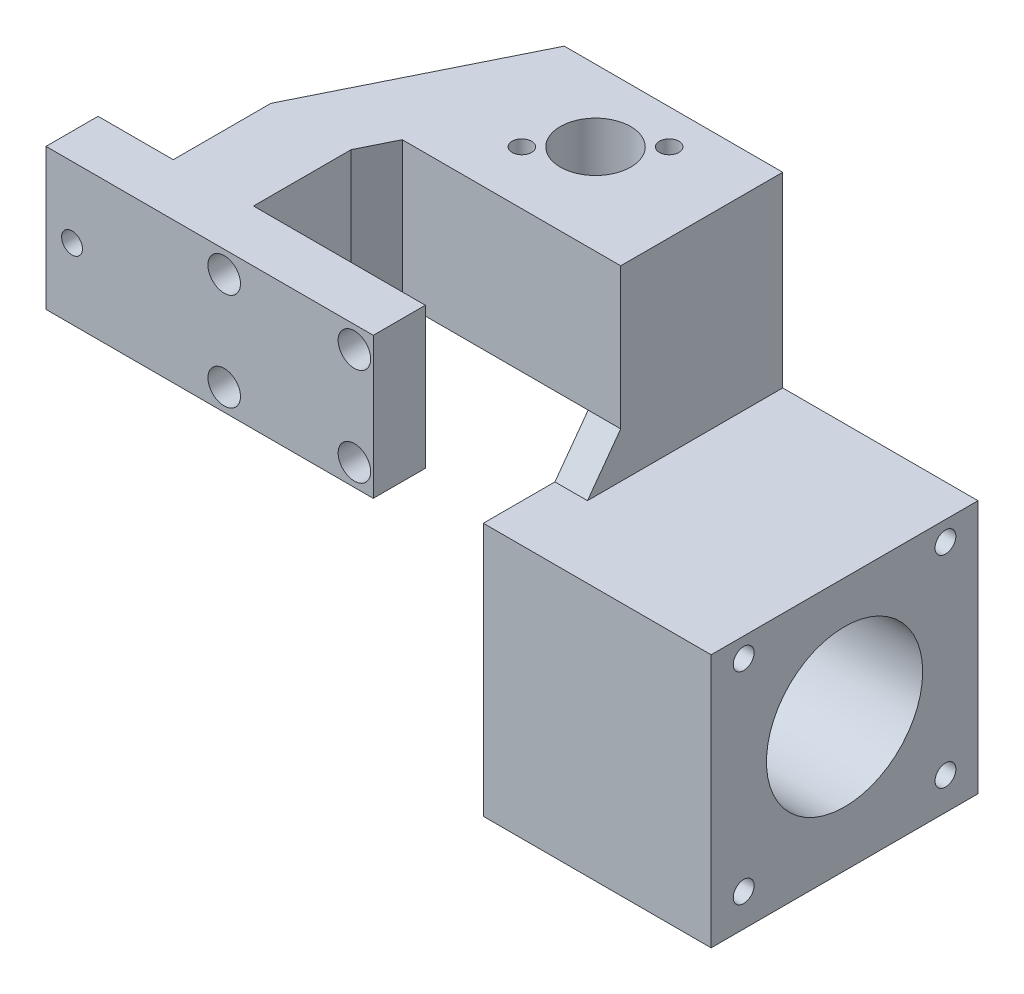
SolidWorks part; units mm, degrees
ref_plane "Přední rovina" through (0, 0, 0) normal (0, 0, 1) x (1, 0, 0)
ref_plane "Horní rovina" through (0, 0, 0) normal (0, 1, 0) x (1, 0, 0)
ref_plane "Pravá rovina" through (0, 0, 0) normal (1, 0, 0) x (0, 0, -1)
sketch "Skica1" plane through (0, 0, 0) normal (0, 0, 1) x (1, 0, 0)
  line L1 (16.212, -19.9414) -> (-34.0669, -19.9414)
  line L2 (16.212, -19.9414) -> (16.212, 1.7586)
  line L3 (16.212, 1.7586) -> (-34.0669, 1.7586)
  line L4 (-34.0669, -19.9414) -> (-34.0669, 1.7586)
  circle A0 centre (13.312, -16.5914) radius 1.6
  circle A1 centre (-6.688, -16.5914) radius 1.6
  circle A2 centre (-6.688, -1.5914) radius 1.6
  circle A3 centre (13.312, -1.5914) radius 1.6
  dimension "D1" = 3.2
  dimension "D2" = 2
  dimension "D3" = 2
extrude "Přidat vysunutím1" add sketch "Skica1" along normal blind 8
sketch "Skica2" plane through (0, 0, 8) normal (0, 0, 1) x (1, 0, 0)
  circle A0 centre (13.312, -16.5914) radius 2.5
  circle A1 centre (-6.688, -16.5914) radius 2.5
  circle A2 centre (-6.688, -1.5914) radius 2.5
  circle A3 centre (13.312, -1.5914) radius 2.5
  dimension "D1" = 5
  dimension "D2" = 2
  dimension "D3" = 2
extrude "Odebrat vysunutím1" cut sketch "Skica2" against normal blind 4
sketch "Skica3" plane through (0, 0, 8) normal (0, 0, 1) x (1, 0, 0)
  line L0 (-34.0669, 1.7586) -> (-34.0669, -19.9414) construction
  circle A0 centre (-30.0669, -9.0914) radius 1.6
  dimension "D1" = 3.2
  dimension "D2" = 4
extrude "Odebrat vysunutím2" cut sketch "Skica3" against normal blind 8
sketch "Skica4" plane through (0, 0, 0) normal (0, 0, -1) x (-1, 0, 0)
  line L0 (-16.212, 1.7586) -> (34.0669, 1.7586) construction
  line L1 (10.188, 1.7586) -> (22.5157, 1.7586)
  line L2 (10.188, 1.7586) -> (10.188, -19.9414)
  line L3 (10.188, -19.9414) -> (22.5157, -19.9414)
  line L4 (22.5157, 1.7586) -> (22.5157, -19.9414)
  line L5 (10.188, 1.7586) -> (10.188, -19.9414) construction
  line L6 (34.0669, -19.9414) -> (-16.212, -19.9414) construction
  line L7 (10.188, -19.9414) -> (10.188, 1.7586) construction
extrude "Přidat vysunutím2" add sketch "Skica4" along normal blind 15
sketch "Skica6" plane through (0, 1.7586, 0) normal (0, 1, 0) x (1, 0, 0)
  line L0 (-10.188, 15) -> (-22.5157, 15)
  line L1 (-10.188, 15) -> (-7.5858, 20.255)
  line L2 (-22.5157, 15) -> (-7.5858, 45.15)
  line L3 (4.7419, 45.15) -> (-7.5858, 45.15)
  line L5 (-7.5858, 45.15) -> (20.9737, 45.15)
  line L7 (-7.5858, 20.255) -> (20.9737, 20.255)
  line L8 (20.9737, 45.15) -> (20.9737, 20.255)
  circle A0 centre (8.2082, 34.15) radius 11 construction
  circle A3 centre (8.2082, 34.15) radius 5.4063
  line M11 (-10.188, 15) -> (-22.5157, 15)
extrude "Přidat vysunutím3" add sketch "Skica6" against normal up to surface (21.7 mm away) contours L8 L5 L3 L2 L1 L7 A3 M11 region at (1.476, 1.7586, -30.6172) up to face at (-12.6397, -19.9414, -1.75)
sketch "Skica7" plane through (0, -19.9414, 0) normal (0, -1, 0) x (1, 0, 0)
  line L0 (8.2082, -34.15) -> (0.2082, -34.15) construction
  line L1 (8.2082, -34.15) -> (2.5514, -28.4931) construction
  line L2 (8.2082, -34.15) -> (13.8651, -39.8069) construction
  circle A0 centre (8.2082, -34.15) radius 8 construction
  circle A1 centre (2.5514, -28.4931) radius 1.5
  circle A2 centre (13.8651, -39.8069) radius 1.5
  point P12 (8.2082, -34.15)
  dimension "D1" = 16
  dimension "D2" = 3
  dimension "D3" = 2
extrude "Odebrat vysunutím3" cut sketch "Skica7" against normal up to surface (21.7 mm away) up to face at (-6.1951, 1.7586, -12.0675)
sketch "Skica9" plane through (20.9737, 0, 0) normal (1, 0, 0) x (0, 0, -1)
  line L0 (20.255, -19.9414) -> (15, -19.9414) construction
  line L1 (40.15, -29.9414) -> (9.15, -29.9414) construction
  line L2 (40.15, -29.9414) -> (40.15, -60.9414) construction
  line L3 (40.15, -60.9414) -> (9.15, -60.9414) construction
  line L4 (9.15, -29.9414) -> (9.15, -60.9414) construction
  line L5 (45.15, 1.7586) -> (20.255, 1.7586)
  line L6 (45.15, 1.7586) -> (45.15, -19.9414)
  line L8 (20.255, 1.7586) -> (20.255, -19.9414)
  line L10 (45.15, -19.9414) -> (45.15, -65.9414)
  line L11 (45.15, -65.9414) -> (15.15, -65.9414)
  line L13 (15.15, -60.9414) -> (15.15, -65.9414)
  line L14 (15.15, -65.9414) -> (4.15, -65.9414)
  line L15 (15.15, -65.9414) -> (15.15, -60.9414)
  line L16 (15.15, -26.9414) -> (4.15, -26.9414)
  line L17 (4.15, -65.9414) -> (4.15, -26.9414)
  line L19 (15.15, -26.9414) -> (20.255, -19.9414)
  line L20 (24.65, -45.4414) -> (9.15, -45.4414) construction
  line L21 (24.65, -45.4414) -> (24.65, -60.9414) construction
  circle A0 centre (40.15, -60.9414) radius 1.6
  circle A1 centre (9.15, -60.9414) radius 1.6
  circle A2 centre (9.15, -29.9414) radius 1.6
  circle A3 centre (40.15, -29.9414) radius 1.6
  circle A4 centre (24.65, -45.4414) radius 12
  line M15 (20.255, 1.7586) -> (20.255, -19.9414)
  line M16 (20.255, -19.9414) -> (45.15, -19.9414)
  line M17 (45.15, -19.9414) -> (45.15, 1.7586)
  line M18 (45.15, 1.7586) -> (20.255, 1.7586)
  dimension "D2" = 3.2
  dimension "D8" = 24
  dimension "D1" = 31
  dimension "D5" = 10
  dimension "D6" = 5
  dimension "D7" = 5
  dimension "D9" = 5
  dimension "D10" = 3
  dimension "D3" = 2
  dimension "D4" = 2
extrude "Přidat vysunutím4" add sketch "Skica9" along normal blind 5 contours M18 M15 M16 M17 | L19 L16 L17 L14 L11 L10 A3 A2 A1 A0 M16 region at (20.9737, -9.0914, -32.7025) region at (20.9737, -42.9414, -44.5338)
sketch "Skica10" plane through (25.9737, 0, 0) normal (1, 0, 0) x (0, 0, -1)
  line L1 (4.15, -26.9414) -> (45.15, -26.9414)
  line L2 (4.15, -26.9414) -> (4.15, -65.9414)
  line L3 (4.15, -65.9414) -> (45.15, -65.9414)
  line L4 (45.15, -26.9414) -> (45.15, -65.9414)
  circle A0 centre (24.65, -45.4414) radius 12 construction
  circle A1 centre (40.15, -60.9414) radius 1.6 construction
  circle A2 centre (40.15, -29.9414) radius 1.6 construction
  circle A3 centre (9.15, -29.9414) radius 1.6 construction
  circle A4 centre (9.15, -60.9414) radius 1.6 construction
  circle A5 centre (24.65, -45.4414) radius 12
  circle A6 centre (40.15, -60.9414) radius 1.6
  circle A7 centre (40.15, -29.9414) radius 1.6
  circle A8 centre (9.15, -29.9414) radius 1.6
  circle A9 centre (9.15, -60.9414) radius 1.6
extrude "Přidat vysunutím5" add sketch "Skica10" along normal blind 30
